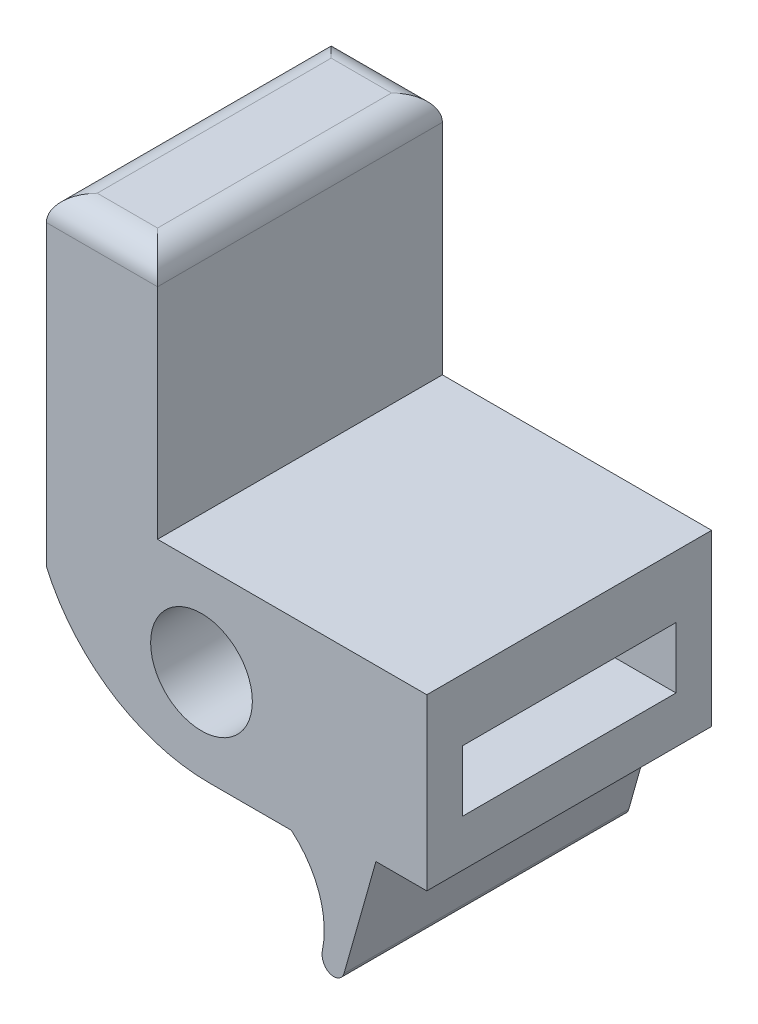
SolidWorks part; units mm, degrees
ref_plane "Alzado" through (0, 0, 0) normal (0, 0, 1) x (1, 0, 0)
ref_plane "Planta" through (0, 0, 0) normal (0, 1, 0) x (1, 0, 0)
ref_plane "Vista lateral" through (0, 0, 0) normal (1, 0, 0) x (0, 0, -1)
sketch "Croquis1" plane through (0, 0, 0) normal (0, 0, 1) x (1, 0, 0)
  line L0 (0, 0) -> (-0.44, 0) construction
  line L1 (-2.99, -1.13) -> (2.99, -1.13)
  line L2 (-2.99, -1.13) -> (-2.99, 1.13)
  line L3 (-2.99, 1.13) -> (2.99, 1.13)
  line L4 (2.99, -1.13) -> (2.99, 1.13)
  line L5 (-2.99, -1.13) -> (2.99, 1.13) construction
  line L6 (-2.99, 1.13) -> (2.99, -1.13) construction
  circle A0 centre (-0.44, 0) radius 1
  point P0 (0, 0)
  dimension "D4" = 2
  dimension "D1" = 5.98
  dimension "D2" = 2.26
  dimension "D3" = 0.44
extrude "Saliente-Extruir1" add sketch "Croquis1" along normal blind 3.2
sketch "Croquis2" plane through (0, 0, 0) normal (0, 0, 1) x (1, 0, 0)
  line L1 (2.99, -1.13) -> (0.81, -1.13)
  line L2 (2.99, -1.13) -> (2.99, -1.51)
  line L3 (2.99, -1.51) -> (0.81, -1.51)
  line L4 (0.81, -1.13) -> (0.81, -1.51)
  dimension "D1" = 0.38
  dimension "D2" = 2.18
extrude "Saliente-Extruir2" add sketch "Croquis2" along normal up to vertex (3.2 mm away) up to point (2.99, -1.13, 3.2)
sketch "Croquis4" plane through (0, 1.13, 0) normal (0, 1, 0) x (1, 0, 0)
  line L0 (2.99, 0) -> (-2.99, 0) construction
  line L1 (-2.99, -3.2) -> (-1.304, -3.2)
  line L2 (-2.99, -3.2) -> (-2.99, 0)
  line L3 (-2.99, 0) -> (-1.304, 0)
  line L4 (-1.304, -3.2) -> (-1.304, 0)
extrude "Saliente-Extruir3" add sketch "Croquis4" along normal blind 5.5
sketch "Croquis5" plane through (0, 0, 0) normal (0, 0, -1) x (-1, 0, 0)
  line L0 (-2.99, -1.51) -> (-2.312, -3.9059)
  line L1 (-0.81, -1.51) -> (-2.99, -1.51) construction
  line L2 (-2.99, -1.51) -> (-0.81, -1.51)
  arc A0 (-0.81, -1.51) -> (-1.8676, -3.8006) centre (-0.173, -3.1935) ccw
  arc A1 (-2.312, -3.9059) -> (-1.8676, -3.8006) centre (-2.1627, -3.5456) ccw
  dimension "D3" = 0.39
  dimension "D1" = 74.2
  dimension "D2" = 2.49
extrude "Saliente-Extruir4" add sketch "Croquis5" against normal up to vertex (3.2 mm away) up to point (2.99, -1.51, 3.2)
fillet "Redondeo2" radius 0.3 1 edges at (1.8676, -3.8006, 1.6)
fillet "Redondeo3" radius 0.21 1 edges at (2.312, -3.9059, 1.6)
sketch "Croquis6" plane through (-2.99, 0, 0) normal (-1, 0, 0) x (0, 0, 1)
  line L4 (0, 6.63) -> (0, -1.13)
  line L5 (0, -1.13) -> (3.2, -1.13)
  line L6 (3.2, -1.13) -> (3.2, 6.63)
  line L7 (3.2, 6.63) -> (0, 6.63)
  line L8 (0, 6.63) -> (0, -1.13)
  line L9 (0, -1.13) -> (3.2, -1.13)
  line L10 (3.2, -1.13) -> (3.2, 6.63)
  line L11 (3.2, 6.63) -> (0, 6.63)
  dimension "D1" = 0
extrude "Saliente-Extruir5" add sketch "Croquis6" along normal blind 0.5
sketch "Croquis7" plane through (0, 0, 0) normal (0, 0, -1) x (-1, 0, 0)
  line L0 (1.304, 6.63) -> (3.49, 6.63) construction
  line L1 (3.49, -1.13) -> (1.304, -1.13)
  line L2 (3.49, -1.13) -> (3.49, 6.63)
  line L3 (3.49, 6.63) -> (1.304, 6.63)
  line L4 (1.304, -1.13) -> (1.304, 6.63)
  line L5 (1.304, 6.63) -> (1.304, 1.13) construction
extrude "Saliente-Extruir6" add sketch "Croquis7" along normal blind 1.6
sketch "Croquis8" plane through (0, 0, 0) normal (0, 0, -1) x (-1, 0, 0)
  line L7 (-0.81, -1.13) -> (1.304, -1.13)
  line L8 (1.304, -1.13) -> (1.304, -0.5035)
  line L9 (1.304, 1.13) -> (-2.99, 1.13)
  line L10 (-2.99, 1.13) -> (-2.99, -1.51)
  line L11 (-2.99, -1.51) -> (-2.3616, -3.7308)
  line L12 (-0.81, -1.51) -> (-0.81, -1.13)
  line L13 (1.304, 0.5035) -> (1.304, 1.13)
  line L14 (-0.81, -1.13) -> (1.304, -1.13)
  line L15 (1.304, -1.13) -> (1.304, -0.5035)
  line L16 (1.304, 1.13) -> (-2.99, 1.13)
  line L17 (-2.99, 1.13) -> (-2.99, -1.51)
  line L18 (-2.99, -1.51) -> (-2.3616, -3.7308)
  line L19 (-0.81, -1.51) -> (-0.81, -1.13)
  line L20 (1.304, 0.5035) -> (1.304, 1.13)
  arc A4 (-2.3616, -3.7308) -> (-1.9955, -3.8047) centre (-2.1595, -3.6736) ccw
  arc A5 (-1.9955, -3.8047) -> (-1.936, -3.5569) centre (-2.2298, -3.6174) ccw
  arc A6 (-0.81, -1.51) -> (-1.936, -3.5569) centre (-0.173, -3.1935) ccw
  arc A7 (1.304, 0.5035) -> (1.304, -0.5035) centre (0.44, 0) ccw
  arc A8 (-2.3616, -3.7308) -> (-1.9955, -3.8047) centre (-2.1595, -3.6736) ccw
  arc A9 (-1.9955, -3.8047) -> (-1.936, -3.5569) centre (-2.2298, -3.6174) ccw
  arc A10 (-0.81, -1.51) -> (-1.936, -3.5569) centre (-0.173, -3.1935) ccw
  arc A11 (1.304, 0.5035) -> (1.304, -0.5035) centre (0.44, 0) ccw
  dimension "D1" = 0
extrude "Saliente-Extruir7" add sketch "Croquis8" along normal up to vertex (1.6 mm away) up to point (-3.49, -1.13, -1.6)
sketch "Croquis9" plane through (0, 0, 0) normal (0, 0, 1) x (1, 0, 0)
  line L1 (-1.304, -0.5035) -> (-1.304, 0.5035)
  line L2 (-1.304, -0.5035) -> (-1.304, 0.5035)
  arc A1 (-1.304, 0.5035) -> (-1.304, -0.5035) centre (-0.44, 0) ccw
  arc A2 (-1.304, 0.5035) -> (-1.304, -0.5035) centre (-0.44, 0) ccw
  dimension "D1" = 0
extrude "Cortar-Extruir2" cut sketch "Croquis9" against normal blind 10
sketch "Croquis11" plane through (2.99, 0, 0) normal (1, 0, 0) x (0, 0, -1)
  line L4 (-3.2, -1.51) -> (1.6, -1.51)
  line L5 (1.6, -1.51) -> (1.6, 1.13)
  line L6 (1.6, 1.13) -> (-3.2, 1.13)
  line L7 (-3.2, 1.13) -> (-3.2, -1.51)
  line L8 (-3.2, -1.51) -> (1.6, -1.51)
  line L9 (1.6, -1.51) -> (1.6, 1.13)
  line L10 (1.6, 1.13) -> (-3.2, 1.13)
  line L11 (-3.2, 1.13) -> (-3.2, -1.51)
  dimension "D1" = 0
extrude "Saliente-Extruir8" add sketch "Croquis11" along normal blind 1
sketch "Croquis13" plane through (0, -1.13, 0) normal (0, -1, 0) x (1, 0, 0)
  line L4 (0.81, 3.2) -> (-3.49, 3.2)
  line L5 (-3.49, 3.2) -> (-3.49, -1.6)
  line L6 (-3.49, -1.6) -> (0.81, -1.6)
  line L7 (0.81, -1.6) -> (0.81, 3.2)
  line L8 (0.81, 3.2) -> (-3.49, 3.2)
  line L9 (-3.49, 3.2) -> (-3.49, -1.6)
  line L10 (-3.49, -1.6) -> (0.81, -1.6)
  line L11 (0.81, -1.6) -> (0.81, 3.2)
  dimension "D1" = 0
sketch "Croquis15" plane through (0, -1.13, 0) normal (0, -1, 0) x (1, 0, 0)
  line L4 (-3.49, -1.6) -> (0.81, -1.6)
  line L5 (0.81, -1.6) -> (0.81, 3.2)
  line L6 (0.81, 3.2) -> (-3.49, 3.2)
  line L7 (-3.49, 3.2) -> (-3.49, -1.6)
  line L8 (-3.49, -1.6) -> (0.81, -1.6)
  line L9 (0.81, -1.6) -> (0.81, 3.2)
  line L10 (0.81, 3.2) -> (-3.49, 3.2)
  line L11 (-3.49, 3.2) -> (-3.49, -1.6)
  dimension "D1" = 0
extrude "Saliente-Extruir10" add sketch "Croquis15" along normal up to vertex (0.38 mm away) up to point (0.81, -1.51, -1.6)
fillet "Redondeo6" radius 3.2 1 edges at (-3.49, -1.51, 0.8)
sketch "Croquis16" plane through (0, 1.13, 0) normal (0, 1, 0) x (1, 0, 0)
  line L4 (-1.304, 1.6) -> (-1.304, -3.2)
  line L5 (-1.304, -3.2) -> (3.99, -3.2)
  line L6 (3.99, -3.2) -> (3.99, 1.6)
  line L7 (3.99, 1.6) -> (-1.304, 1.6)
  line L8 (-1.304, 1.6) -> (-1.304, -3.2)
  line L9 (-1.304, -3.2) -> (3.99, -3.2)
  line L10 (3.99, -3.2) -> (3.99, 1.6)
  line L11 (3.99, 1.6) -> (-1.304, 1.6)
  dimension "D1" = 0
extrude "Saliente-Extruir11" add sketch "Croquis16" along normal blind 0.4
sketch "Croquis18" plane through (0, 0, -1.6) normal (0, 0, -1) x (-1, 0, 0)
  line L8 (-0.81, -1.51) -> (0.29, -1.51)
  line L9 (3.49, 1.69) -> (3.49, 6.63)
  line L10 (3.49, 6.63) -> (1.304, 6.63)
  line L11 (1.304, 6.63) -> (1.304, 1.53)
  line L12 (1.304, 1.53) -> (-3.99, 1.53)
  line L13 (-3.99, 1.53) -> (-3.99, -1.51)
  line L14 (-3.99, -1.51) -> (-2.99, -1.51)
  line L15 (-2.99, -1.51) -> (-2.3616, -3.7308)
  line L16 (-0.81, -1.51) -> (0.29, -1.51)
  line L17 (3.49, 1.69) -> (3.49, 6.63)
  line L18 (3.49, 6.63) -> (1.304, 6.63)
  line L19 (1.304, 6.63) -> (1.304, 1.53)
  line L20 (1.304, 1.53) -> (-3.99, 1.53)
  line L21 (-3.99, 1.53) -> (-3.99, -1.51)
  line L22 (-3.99, -1.51) -> (-2.99, -1.51)
  line L23 (-2.99, -1.51) -> (-2.3616, -3.7308)
  circle A0 centre (0.44, 0) radius 1 construction
  circle A1 centre (0.44, 0) radius 1
  arc A4 (0.29, -1.51) -> (3.49, 1.69) centre (0.29, 1.69) ccw
  arc A5 (-2.3616, -3.7308) -> (-1.9955, -3.8047) centre (-2.1595, -3.6736) ccw
  arc A6 (-1.9955, -3.8047) -> (-1.936, -3.5569) centre (-2.2298, -3.6174) ccw
  arc A7 (-0.81, -1.51) -> (-1.936, -3.5569) centre (-0.173, -3.1935) ccw
  arc A8 (0.29, -1.51) -> (3.49, 1.69) centre (0.29, 1.69) ccw
  arc A9 (-2.3616, -3.7308) -> (-1.9955, -3.8047) centre (-2.1595, -3.6736) ccw
  arc A10 (-1.9955, -3.8047) -> (-1.936, -3.5569) centre (-2.2298, -3.6174) ccw
  arc A11 (-0.81, -1.51) -> (-1.936, -3.5569) centre (-0.173, -3.1935) ccw
  dimension "D1" = 0
extrude "Saliente-Extruir12" add sketch "Croquis18" along normal blind 0.8
fillet "Redondeo7" radius 0.5 4 edges at (-2.397, 6.63, 3.2) (-3.49, 6.63, 0.4) (-2.397, 6.63, -2.4) (-1.304, 6.63, 0.4)
sketch "Croquis19" plane through (3.99, 0, 0) normal (1, 0, 0) x (0, 0, -1)
  line L0 (-0.4, -1.51) -> (-0.4, -0.59) construction
  line L1 (-2.5, 0.61) -> (1.7, 0.61)
  line L2 (-2.5, 0.61) -> (-2.5, -0.59)
  line L3 (-2.5, -0.59) -> (1.7, -0.59)
  line L4 (1.7, 0.61) -> (1.7, -0.59)
  line L5 (-3.2, -1.51) -> (2.4, -1.51) construction
  line L6 (2.4, 0.01) -> (1.7, 0.01) construction
  line L7 (2.4, 1.53) -> (2.4, -1.51) construction
  dimension "D1" = 1.2
  dimension "D2" = 4.2
extrude "Cortar-Extruir3" cut sketch "Croquis19" against normal blind 3
sketch "Croquis20" plane through (0, 0, 3.2) normal (0, 0, 1) x (1, 0, 0)
  line L0 (-1.304, 6.13) -> (-1.304, 1.53) construction
  line L1 (-1.304, 1.83) -> (3.99, 1.83)
  line L2 (-1.304, 1.83) -> (-1.304, 1.53)
  line L3 (-1.304, 1.53) -> (3.99, 1.53)
  line L4 (3.99, 1.83) -> (3.99, 1.53)
  line L6 (-3.49, 1.69) -> (-3.49, 0.2723)
  line L7 (0.81, -1.81) -> (-0.29, -1.81)
  line L8 (1.3245, -1.81) -> (-0.29, -1.81)
  line L9 (0.81, -1.51) -> (-0.29, -1.51) construction
  line L10 (0.81, -1.51) -> (-0.29, -1.51)
  arc A2 (-3.49, 1.69) -> (-0.29, -1.51) centre (-0.29, 1.69) ccw construction
  arc A3 (-3.79, 1.69) -> (-0.29, -1.81) centre (-0.29, 1.69) ccw
  arc A4 (-3.49, 0.2723) -> (-0.29, -1.81) centre (-0.29, 1.69) ccw
  arc A5 (1.936, -3.5569) -> (0.81, -1.51) centre (0.173, -3.1935) ccw construction
  arc A6 (-3.49, 1.69) -> (-0.29, -1.51) centre (-0.29, 1.69) ccw
  arc A7 (1.3245, -1.81) -> (0.81, -1.51) centre (0.173, -3.1935) ccw
  dimension "D1" = 0.3
  dimension "D2" = 0.3
extrude "Saliente-Extruir13" add sketch "Croquis20" against normal up to surface (5.6 mm away) up to face at (0.6587, -0.058, -2.4)
